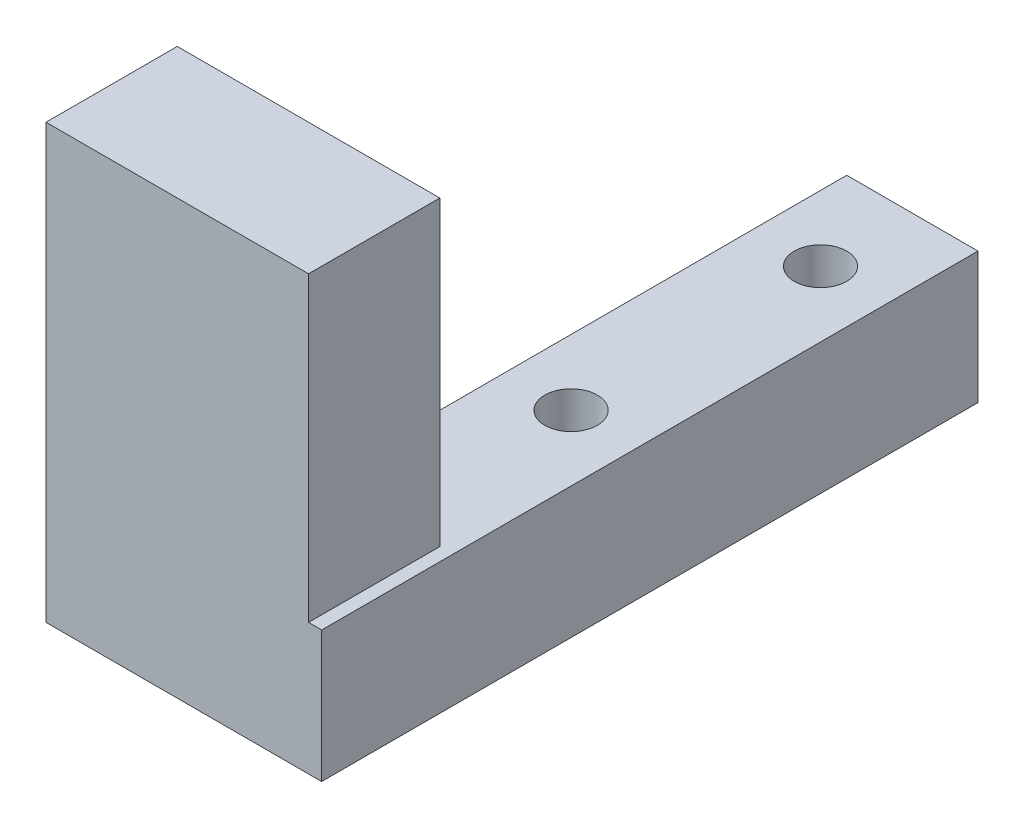
SolidWorks part; units mm, degrees
ref_plane "Front Plane" through (0, 0, 0) normal (0, 0, 1) x (1, 0, 0)
ref_plane "Top Plane" through (0, 0, 0) normal (0, 1, 0) x (1, 0, 0)
ref_plane "Right Plane" through (0, 0, 0) normal (1, 0, 0) x (0, 0, -1)
sketch "Sketch1" plane through (0, 0, 0) normal (0, 0, 1) x (1, 0, 0)
  line L1 (-7.8513, 3.6433) -> (2.1487, 3.6433)
  line L2 (-7.8513, 3.6433) -> (-7.8513, -6.3567)
  line L3 (-7.8513, -6.3567) -> (2.1487, -6.3567)
  line L4 (2.1487, 3.6433) -> (2.1487, -6.3567)
  dimension "D1" = 10
  dimension "D2" = 10
extrude "Boss-Extrude1" add sketch "Sketch1" along normal blind 50
sketch "Sketch3" plane through (-7.8513, 0, 0) normal (-1, 0, 0) x (0, 0, 1)
  line L0 (50, -6.3567) -> (0, -6.3567) construction
  line L1 (50, 3.6433) -> (40, 3.6433)
  line L2 (50, 3.6433) -> (50, -6.3567)
  line L3 (50, -6.3567) -> (40, -6.3567)
  line L4 (40, 3.6433) -> (40, -6.3567)
  dimension "D1" = 10
  dimension "D2" = 10
extrude "Boss-Extrude3" add sketch "Sketch3" along normal blind 11
sketch "Sketch8" plane through (0, 3.6433, 0) normal (0, 1, 0) x (1, 0, 0)
  line L1 (-18.8513, -50) -> (1.1487, -50)
  line L2 (-18.8513, -50) -> (-18.8513, -40)
  line L3 (-18.8513, -40) -> (1.1487, -40)
  line L4 (1.1487, -50) -> (1.1487, -40)
  dimension "D1" = 20
extrude "Boss-Extrude4" add sketch "Sketch8" along normal blind 23
sketch "Sketch9" plane through (0, 3.6433, 0) normal (0, 1, 0) x (1, 0, 0)
  line L0 (-2.8513, 0) -> (-2.8513, -5)
  line L3 (2.1487, 0) -> (-7.8513, 0) construction
  line L4 (-2.8513, -5) -> (-2.8513, -7)
  line L5 (-2.8513, -9) -> (-2.8513, -24)
  line L6 (-2.8513, -24) -> (-2.8513, -26)
  line L7 (2.1487, -50) -> (2.1487, 0) construction
  circle A0 centre (-2.8513, -7) radius 2
  circle A1 centre (-2.8513, -26) radius 2
  dimension "D1" = 5
  dimension "D3" = 15
  dimension "D2" = 2
  dimension "D4" = 2
extrude "Cut-Extrude2" cut sketch "Sketch9" against normal blind 23 contours A0
extrude "Cut-Extrude3" cut sketch "Sketch9<4>" against normal blind 23 contours A1
sketch "Sketch9<4>" plane through (0, 3.6433, 0) normal (0, 1, 0) x (1, 0, 0) same geometry as "Sketch9"
